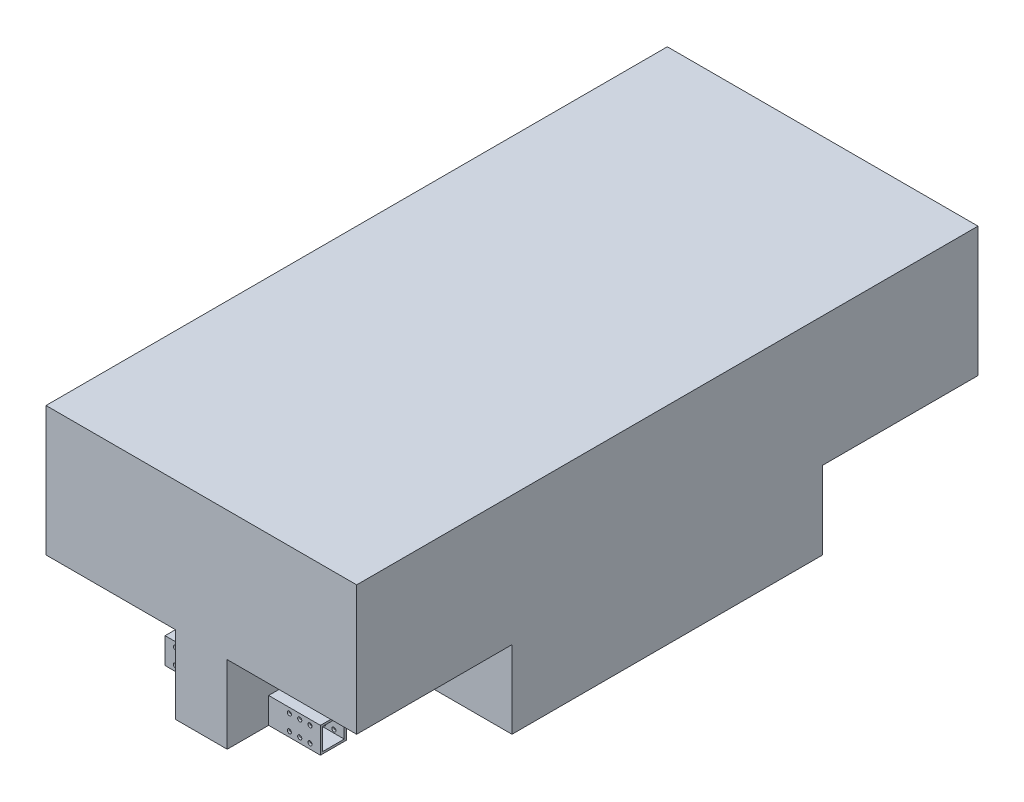
SolidWorks part; units mm, degrees
ref_plane "Front Plane" through (0, 0, 0) normal (0, 0, 1) x (1, 0, 0)
ref_plane "Top Plane" through (0, 0, 0) normal (0, 1, 0) x (1, 0, 0)
ref_plane "Right Plane" through (0, 0, 0) normal (1, 0, 0) x (0, 0, -1)
sketch "Sketch2" plane through (0, 0, 0) normal (1, 0, 0) x (0, 0, -1)
  line L1 (-300, 100) -> (300, 100)
  line L2 (-300, 100) -> (-300, -100)
  line L3 (-300, -100) -> (300, -100)
  line L4 (300, 100) -> (300, -100)
  line L5 (-300, 100) -> (300, -100) construction
  line L6 (-300, -100) -> (300, 100) construction
  point P0 (0, 0)
  dimension "D1" = 600
  dimension "D2" = 200
extrude "Boss-Extrude1" add sketch "Sketch2" along normal blind 150 and the other way blind 150
sketch "Sketch3" plane through (150, 0, 0) normal (1, 0, 0) x (0, 0, -1)
  line L1 (-300, -100) -> (-150, -100)
  line L2 (-300, -100) -> (-300, -25)
  line L3 (-300, -25) -> (-150, -25)
  line L4 (-150, -100) -> (-150, -25)
  line L5 (300, -100) -> (150, -100)
  line L6 (300, -100) -> (300, -25)
  line L7 (300, -25) -> (150, -25)
  line L8 (150, -100) -> (150, -25)
  dimension "D1" = 150
  dimension "D2" = 150
  dimension "D3" = 75
  dimension "D4" = 75
extrude "Cut-Extrude1" cut sketch "Sketch3" against normal blind 125
mirror "Mirror1" about plane through (0, 0, 0) normal (1, 0, 0) of "Cut-Extrude1"
sketch "Sketch4" plane through (25, 0, 0) normal (1, 0, 0) x (0, 0, -1)
  line L0 (-300, -100) -> (-150, -100) construction
  line L1 (-260, -75) -> (-235, -75)
  line L2 (-260, -75) -> (-260, -100)
  line L3 (-260, -100) -> (-235, -100)
  line L4 (-235, -75) -> (-235, -100)
  line L5 (-300, -25) -> (-300, -100) construction
  line L6 (-258, -77) -> (-258, -98)
  line L7 (-258, -98) -> (-237, -98)
  line L8 (-237, -77) -> (-237, -98)
  line L9 (-258, -77) -> (-237, -77)
  dimension "D1" = 25
  dimension "D2" = 25
  dimension "D3" = 0
  dimension "D4" = 40
  dimension "D5" = 2
extrude "Boss-Extrude2" add sketch "Sketch4" along normal blind 50
sketch "Sketch5" plane through (0, 0, 260) normal (0, 0, 1) x (1, 0, 0)
  line L0 (75, -75) -> (25, -75) construction
  line L1 (75, -100) -> (25, -100) construction
  line L2 (75, -75) -> (75, -100) construction
  circle A0 centre (65, -80) radius 2
  circle A1 centre (55, -80) radius 2
  circle A2 centre (45, -80) radius 2
  circle A3 centre (65, -95) radius 2
  circle A4 centre (55, -95) radius 2
  circle A5 centre (45, -95) radius 2
  dimension "D1" = 5
  dimension "D2" = 5
  dimension "D3" = 5
  dimension "D4" = 5
  dimension "D5" = 5
  dimension "D6" = 5
  dimension "D7" = 10
  dimension "D8" = 10
  dimension "D9" = 10
  dimension "D10" = 10
  dimension "D11" = 10
  dimension "D12" = 10
extrude "Cut-Extrude2" cut sketch "Sketch5" against normal blind 25
mirror "Mirror2" about plane through (0, 0, 0) normal (1, 0, 0) of "Cut-Extrude2", "Boss-Extrude2"
mirror "Mirror3" about plane through (0, 0, 0) normal (0, 0, 1) of "Mirror2"
